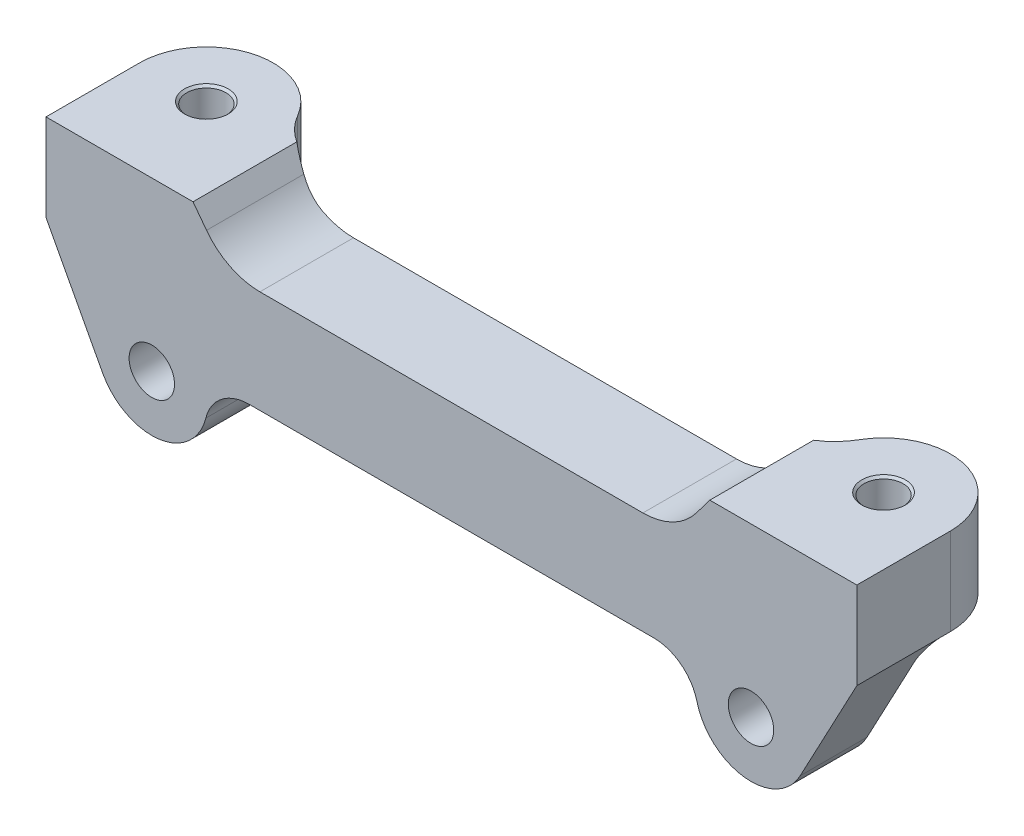
SolidWorks part; units mm, degrees
material "6061-T6 (SS)"
ref_plane "Front Plane" through (0, 0, 0) normal (0, 0, 1) x (1, 0, 0)
ref_plane "Top Plane" through (0, 0, 0) normal (0, 1, 0) x (1, 0, 0)
ref_plane "Right Plane" through (0, 0, 0) normal (1, 0, 0) x (0, 0, -1)
sketch "Sketch1" plane through (0, 0, 0) normal (0, 0, 1) x (1, 0, 0)
  line L0 (-78.2826, -5.8764) -> (-91, 18)
  line L1 (78.2826, -5.8764) -> (91, 18)
  line L2 (-91, 18) -> (91, 18)
  line L3 (-67.25, 0) -> (67.25, 0) construction
  line L4 (-67.25, 49.4683) -> (-67.25, -38.5169) construction
  line L5 (-111.0705, 12.1936) -> (120.3077, 12.1936) construction
  line L6 (-76, 95.984) -> (-76, -61.4214) construction
  line L7 (76, 97.8887) -> (76, -96.9933) construction
  line L8 (-10.814, 4.5) -> (8.8039, 4.5) construction
  line L9 (-86.2603, -12.5) -> (-78.2603, -12.5) construction
  line L10 (-45.4326, 4.5) -> (45.4326, 4.5)
  circle A0 centre (-67.25, 0) radius 5.1
  circle A1 centre (67.25, 0) radius 5.1
  arc A2 (-78.2826, -5.8764) -> (-55.1292, -3.0556) centre (-67.25, 0) ccw
  arc A3 (55.1292, -3.0556) -> (78.2826, -5.8764) centre (67.25, 0) ccw
  arc A4 (55.1292, -3.0556) -> (45.4326, 4.5) centre (45.4326, -5.5) ccw
  arc A5 (-45.4326, 4.5) -> (-55.1292, -3.0556) centre (-45.4326, -5.5) ccw
  dimension "D1" = 10.2
  dimension "D3" = 12.5
  dimension "D4" = 12.5
  dimension "D7" = 15
  dimension "D5" = 10
  dimension "D2" = 134.5
  dimension "D6" = 17
  dimension "D8" = 152
  dimension "D9" = 76
  dimension "D10" = 30.5
extrude "Boss-Extrude1" add sketch "Sketch1" along normal blind 11
sketch "Sketch2" plane through (0, 18, 0) normal (0, 1, 0) x (1, 0, 0)
  line L0 (-91, 10) -> (110.7304, 10) construction
  line L1 (-91, -11) -> (91, -11)
  line L2 (-91, -11) -> (-91, 0)
  line L4 (91, -11) -> (91, 0)
  line L5 (-91.5934, -36.86) -> (92.0021, -36.86) construction
  line L6 (91, -11) -> (-91, -11) construction
  line L7 (91, -11) -> (91, 0) construction
  line L8 (-91, -11) -> (-91, 0) construction
  line L9 (91, 0) -> (-91, 0) construction
  line L10 (-91, 0) -> (-91, 10)
  line L11 (0, 51.6985) -> (0, -30.3083) construction
  line L12 (91, 0) -> (91, 10)
  line L14 (-50.0192, 10) -> (50.0192, 10)
  circle A0 centre (-76, 10) radius 4.4
  circle A1 centre (76, 10) radius 4.4
  arc A2 (-63.0096, 17.5) -> (-91, 10) centre (-76, 10) ccw
  arc A3 (91, 10) -> (63.0096, 17.5) centre (76, 10) ccw
  arc A4 (50.0192, 10) -> (63.0096, 17.5) centre (50.0192, 25) ccw
  arc A5 (-63.0096, 17.5) -> (-50.0192, 10) centre (-50.0192, 25) ccw
  point P19 (0, 0)
  point P32 (91, 16)
  point P35 (-91, 16)
  dimension "D3" = 8.8
  dimension "D5" = 8.8
  dimension "D9" = 0
  dimension "D10" = 30
  dimension "D6" = 15
  dimension "D8" = 15
  dimension "D1" = 21
  dimension "D2" = 152
  dimension "D4" = 46.86
  dimension "D7" = 76
extrude "Boss-Extrude2" add sketch "Sketch2" along normal blind 19.57
sketch "Sketch3" plane through (0, 37.57, 0) normal (0, 1, 0) x (1, 0, 0)
  line L0 (-92.2368, 10) -> (110.7304, 10) construction
  line L2 (-91, -11) -> (91, -11) construction
  line L6 (-91.5934, -36.86) -> (91, -36.86) construction
  line L7 (91, -11) -> (91, 10) construction
  circle A0 centre (-76, 10) radius 5.1
  circle A1 centre (76, 10) radius 5.1
  point P8 (0, -11)
  dimension "D1" = 152
  dimension "D2" = 10.2
  dimension "D4" = 76
  dimension "D5" = 10.2
  dimension "D3" = 46.86
  dimension "D6" = 21
ref_plane "Hub Face (11mm used for 66mm offset)" through (0, 0, 62.5) normal (0, 0, 1) x (1, 0, 0)
ref_plane "Mounting Offset" through (0, 0, 36.86) normal (0, 0, -1) x (-1, 0, 0)
chamfer "Chamfer2" distance 0.5 angle 45 2 edges at (-80.4, 37.57, -10) (71.6, 37.57, -10)
sketch "Sketch4" plane through (0, 0, 0) normal (0, 0, -1) x (-1, 0, 0)
  line L1 (0, 20.9279) -> (0, -20.4836) construction
  line L2 (78.2826, -5.8764) -> (91, 18)
  line L3 (-91, 18) -> (-78.2826, -5.8764)
  line L4 (91, 18) -> (-91, 18)
  line L5 (-91, 18) -> (91, 18) construction
  line L6 (-45.4326, 4.5) -> (45.4326, 4.5)
  circle A0 centre (-67.25, 0) radius 5.1
  circle A1 centre (67.25, 0) radius 5.1 construction
  arc A2 (-55.1292, -3.0556) -> (-78.2826, -5.8764) centre (-67.25, 0) cw
  arc A3 (55.1292, -3.0556) -> (78.2826, -5.8764) centre (67.25, 0) ccw
  arc A4 (55.1292, -3.0556) -> (45.4326, 4.5) centre (45.4326, -5.5) ccw
  circle A5 centre (67.25, 0) radius 5.1
  arc A6 (-45.4326, 4.5) -> (-55.1292, -3.0556) centre (-45.4326, -5.5) ccw
  arc A7 (55.1292, -3.0556) -> (78.2826, -5.8764) centre (67.25, 0) ccw construction
extrude "Boss-Extrude3" add sketch "Sketch4" along normal blind 4
chamfer "Chamfer3" distance 1 angle 45 2 edges at (-72.35, 0, -4) (72.35, 0, -4)
fillet "Fillet6" [suppressed] radius 2.5
ref_plane "Knuckle Mounting Face" through (0, 0, -4) normal (0, 0, -1) x (-1, 0, 0)
fillet "Fillet7" [suppressed] radius 2
fillet "Fillet9" [suppressed] radius 2
sketch "Sketch6" plane through (0, 0, -10) normal (0, 0, -1) x (-1, 0, 0)
  line L0 (-58, 37.57) -> (58, 37.57)
  line L1 (-50.0192, 37.57) -> (50.0192, 37.57) construction
  line L2 (-58, 37.57) -> (-54.9603, 33.5389)
  line L3 (-42.9837, 27.57) -> (42.9837, 27.57)
  line L4 (54.9603, 33.5389) -> (58, 37.57)
  line L7 (-76, 36.3024) -> (-76, 71.4904) construction
  line L8 (76, 71.4904) -> (76, 36.3024) construction
  line L9 (0, -5.3482) -> (0, 71.4904) construction
  arc A0 (42.9837, 27.57) -> (54.9603, 33.5389) centre (42.9837, 42.57) ccw
  arc A1 (-54.9603, 33.5389) -> (-42.9837, 27.57) centre (-42.9837, 42.57) ccw
  dimension "D6" = 15
  dimension "D1" = 152
  dimension "D2" = 76
  dimension "D3" = 18
  dimension "D4" = 18
  dimension "D5" = 10
extrude "Cut-Extrude2" cut sketch "Sketch6" against normal up to surface and the other way blind 10 up to face at (-62.15, 0, 11)
fillet "Fillet12" [suppressed] radius 5
sketch "Sketch7" [suppressed] plane through (0, 48.1486, 0) normal (0, 1, 0) x (1, 0, 0)
  line L0 (0, 30.8967) -> (0, -21.9363) construction
  line L1 (-89, -11) -> (-58, -11)
  line L2 (-89, -11) -> (-58, -11) construction
  line L3 (-91.1073, -6) -> (-91, -9)
  line L4 (-58, -6) -> (-91.1073, -6)
  line L5 (58, -6) -> (58, -11)
  line L6 (58, -6) -> (91.1073, -6)
  line L7 (91.1073, -6) -> (91, -9)
  line L8 (89, -11) -> (58, -11)
  line L9 (-58, -6) -> (-58, -11)
  arc A1 (91, -9) -> (89, -11) centre (89, -9) cw
  arc A3 (-91, -9) -> (-89, -11) centre (-89, -9) ccw
  dimension "D1" = 5
fillet "Fillet13" radius 4 1 edges at (0, 18, -4)
equation "\"D4@Sketch3\"=\"D1@Sketch3\"/2"
equation "\"D7@Sketch2\" = \"D2@Sketch2\" / 2"
equation "\"D9@Sketch1\"=\"D8@Sketch1\"/2"
equation "\"D2@Sketch6\"=\"D1@Sketch6\"/2"
equation "\"D4@Sketch6\"=\"D3@Sketch6\""
